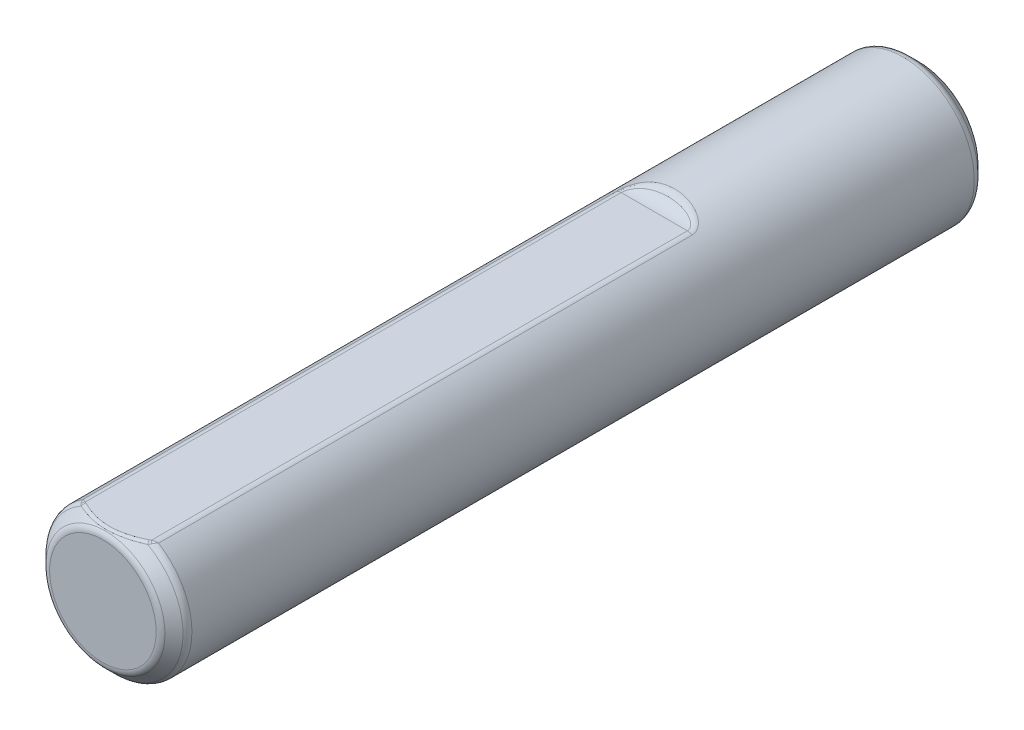
SolidWorks part; units mm, degrees
material "Alloy Steel"
ref_plane "Front" through (0, 0, 0) normal (0, 0, 1) x (1, 0, 0)
ref_plane "Top" through (0, 0, 0) normal (0, 1, 0) x (1, 0, 0)
ref_plane "Right" through (0, 0, 0) normal (1, 0, 0) x (0, 0, -1)
sketch "Sketch1" plane through (0, 0, 0) normal (0, 0, 1) x (1, 0, 0)
  circle A0 centre (0, 0) radius 3.175
  dimension "D1" = 6.35
extrude "Extrude1" add sketch "Sketch1" along normal mid plane 36.5125
chamfer "Chamfer1" distance 0.635 angle 45 2 edges at (3.175, 0, -18.2562) (3.175, 0, 18.2562)
ref_plane "Plane1" through (0, 0, -7.1438) normal (0, 0, 1) x (1, 0, 0)
sketch "Sketch13" plane through (0, 0, -7.1438) normal (0, 0, 1) x (1, 0, 0)
  line L3 (-1.5875, 2.7496) -> (1.5875, 2.7496)
  circle A0 centre (0, 0) radius 3.175 construction
  arc A1 (1.5875, 2.7496) -> (-1.5875, 2.7496) centre (0, 0) ccw
  dimension "D1" = 3.175
extrude "Extrude7" cut sketch "Sketch13" along normal through all
fillet "Fillet1" radius 0.7937 1 edges at (0, 2.7496, -7.1438)
fillet "Fillet3" radius 0.3969 7 edges at (1.5875, 2.7496, 5.6356) (0, 3.175, -7.0531) (2.54, 0, -18.2562) (3.175, 0, -17.6212) (2.54, 0, 18.2562) (0, -3.175, 17.6212) (-1.5875, 2.7496, 5.6356)
fillet "Fillet4" radius 0.1984 5 edges at (1.625, 2.7211, 17.5232) (-1.625, 2.7211, 17.5232) (-0.0358, 2.7496, 18.0464)
equation "\"D1@Chamfer1\" = \"D1@Sketch1\" * .1"
equation "\"D1@Sketch13\" = \"D1@Sketch1\" * .5"
